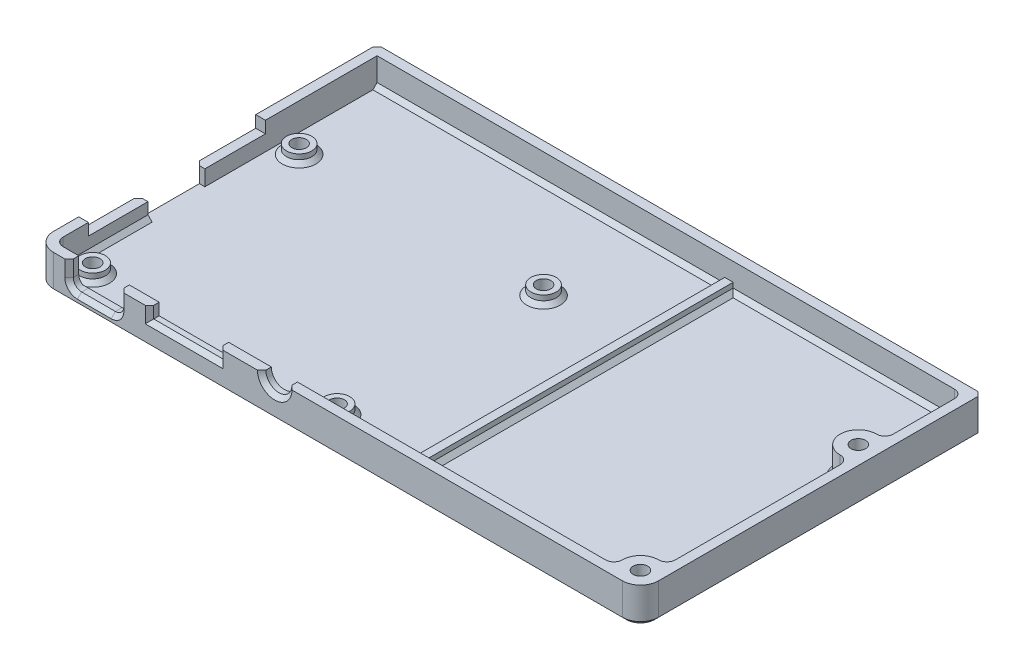
SolidWorks part; units mm, degrees
ref_plane "Front Plane" through (0, 0, 0) normal (0, 0, 1) x (1, 0, 0)
ref_plane "Top Plane" through (0, 0, 0) normal (0, 1, 0) x (1, 0, 0)
ref_plane "Right Plane" through (0, 0, 0) normal (1, 0, 0) x (0, 0, -1)
sketch "Sketch1" plane through (0, 0, 0) normal (0, 1, 0) x (1, 0, 0)
  line L0 (-71.5618, 12.356) -> (65.4382, 12.356) construction
  line L1 (-71.5618, 49.606) -> (65.4382, 49.606)
  line L2 (-71.5618, 49.606) -> (-71.5618, -24.894)
  line L3 (-71.5618, -24.894) -> (65.4382, -24.894)
  line L4 (65.4382, 49.606) -> (65.4382, -24.894)
  line L5 (-60.6618, -24.894) -> (-60.6618, -31.6828) construction
  line L6 (-68.0618, 27.606) -> (-10.0618, 27.606)
  line L7 (-68.0618, 27.606) -> (-68.0618, -21.394)
  line L8 (-68.0618, -21.394) -> (-10.0618, -21.394)
  line L9 (-10.0618, 27.606) -> (-10.0618, -21.394)
  line L10 (-39.5618, -24.894) -> (-39.5618, -31.6828) construction
  line L11 (-18.0618, -24.894) -> (-18.0618, -31.6828) construction
  line L12 (-65.4118, -26.5648) -> (-55.9118, -26.5648) construction
  line L13 (-48.0618, -26.5648) -> (-31.0618, -26.5648) construction
  line L14 (-22.0618, -26.5648) -> (-14.0618, -26.5648) construction
  line L15 (-72.5618, 9.606) -> (-72.5618, -3.394) construction
  line L16 (-71.5618, 12.356) -> (-72.5618, 12.356) construction
  line L17 (-1.5618, 50.5866) -> (-1.5618, 32.5866)
  line L18 (-71.5618, 50.5866) -> (-6.5618, 50.5866)
  line L19 (-71.5618, 50.5866) -> (-71.5618, 32.5866)
  line L20 (-71.5618, 32.5866) -> (-6.5618, 32.5866)
  line L21 (-6.5618, 50.5866) -> (-6.5618, 32.5866)
  line L22 (-1.5618, 32.5866) -> (63.4382, 32.5866)
  line L23 (-1.5618, 50.5866) -> (63.4382, 50.5866)
  line L24 (63.4382, 50.5866) -> (63.4382, 32.5866)
  dimension "D1" = 137
  dimension "D2" = 74.5
  dimension "D3" = 49
  dimension "D4" = 58
  dimension "D5" = 3.5
  dimension "D6" = 3.5
  dimension "D7" = 10.9
  dimension "D8" = 32
  dimension "D9" = 53.5
  dimension "D10" = 2
  dimension "D11" = 13
  dimension "D12" = 9.5
  dimension "D13" = 17
  dimension "D14" = 8
  dimension "D15" = 65
  dimension "D16" = 18
sketch "Sketch3" plane through (0, 0, 0) normal (0, 1, 0) x (1, 0, 0)
  line L4 (68.7382, 52.906) -> (-74.8618, 52.906)
  line L5 (-74.8618, 52.906) -> (-74.8618, -28.194)
  line L6 (-74.8618, -28.194) -> (68.7382, -28.194)
  line L7 (68.7382, -28.194) -> (68.7382, 52.906)
  line L8 (66.4382, 50.606) -> (-72.5618, 50.606)
  line L9 (66.4382, -25.894) -> (66.4382, 50.606)
  line L10 (-72.5618, -25.894) -> (66.4382, -25.894)
  line L11 (-72.5618, 50.606) -> (-72.5618, -25.894)
  line L12 (66.4382, 50.606) -> (-72.5618, 50.606)
  line L13 (66.4382, -25.894) -> (66.4382, 50.606)
  line L14 (-72.5618, -25.894) -> (66.4382, -25.894)
  line L15 (-72.5618, 50.606) -> (-72.5618, -25.894)
  line L16 (-3.0618, 12.356) -> (-3.0618, 52.906) construction
  line L17 (-71.5618, 12.356) -> (65.4382, 12.356) construction
  line L20 (-74.8618, 12.356) -> (52.7382, 12.356) construction
  line L25 (68.7382, -28.194) -> (68.7382, 52.906) construction
  line L26 (66.4382, -25.894) -> (66.4382, 50.606) construction
  dimension "D1" = 1
  dimension "D2" = 2.3
extrude "Boss-Extrude1" add sketch "Sketch3" along normal blind 8.5
sketch "Sketch5" plane through (0, 0, 0) normal (0, 1, 0) x (1, 0, 0)
  line L1 (-72.5618, 50.606) -> (66.4382, 50.606)
  line L2 (-72.5618, 50.606) -> (-72.5618, -25.894)
  line L3 (-72.5618, -25.894) -> (66.4382, -25.894)
  line L4 (66.4382, 50.606) -> (66.4382, -25.894)
extrude "Boss-Extrude2" add sketch "Sketch5" along normal blind 2
sketch "Sketch6" plane through (0, 2, 0) normal (0, 1, 0) x (1, 0, 0)
  circle A0 centre (-68.0618, 27.606) radius 3
  circle A1 centre (-68.0618, -21.394) radius 3
  circle A2 centre (-10.0618, -21.394) radius 3
  circle A3 centre (-10.0618, 27.606) radius 3
extrude "Boss-Extrude3" add sketch "Sketch6" along normal blind 2.2
sketch "Sketch10" plane through (0, 2, 0) normal (0, 1, 0) x (1, 0, 0)
  line L0 (66.4382, 50.606) -> (-72.5618, 50.606) construction
  line L1 (9.9382, 50.606) -> (11.9382, 50.606)
  line L2 (9.9382, 50.606) -> (9.9382, -25.894)
  line L3 (9.9382, -25.894) -> (11.9382, -25.894)
  line L4 (11.9382, 50.606) -> (11.9382, -25.894)
  line L5 (-72.5618, -25.894) -> (66.4382, -25.894) construction
  line L6 (-10.0618, 27.606) -> (-10.0618, -21.394) construction
  dimension "D1" = 2
  dimension "D2" = 20
extrude "Boss-Extrude4" add sketch "Sketch10" along normal blind 2.2
sketch "Sketch11" plane through (0, 0, 28.194) normal (0, 0, 1) x (1, 0, 0)
  line L0 (-74.8618, 8.5) -> (-74.8618, 0) construction
  line L1 (-66.8618, 8.5) -> (-54.8618, 8.5)
  line L2 (-66.8618, 8.5) -> (-66.8618, 2.7)
  line L3 (-66.8618, 2.7) -> (-54.8618, 2.7)
  line L4 (-54.8618, 8.5) -> (-54.8618, 2.7)
  line L5 (-74.8618, 0) -> (68.7382, 0) construction
  line L6 (-60.8618, 8.5) -> (-60.6618, 0) construction
  line L7 (-65.4118, 0) -> (-55.9118, 0) construction
  line L9 (-47.778, 8.5) -> (-31.278, 8.5)
  line L10 (-47.778, 8.5) -> (-47.778, 5.7)
  line L11 (-47.778, 5.7) -> (-31.278, 5.7)
  line L12 (-31.278, 8.5) -> (-31.278, 5.7)
  line L13 (-68.0618, 0) -> (-10.0618, 0) construction
  line L14 (-39.5618, 0) -> (-39.528, 8.5) construction
  line L15 (-48.0618, 0) -> (-31.0618, 0) construction
  line L16 (-18.0618, 0) -> (-18.0618, 8.5) construction
  line L17 (-22.0618, 0) -> (-14.0618, 0) construction
  line L18 (-74.8618, 8.5) -> (68.7382, 8.5) construction
  circle A0 centre (-18.0618, 8.5) radius 3.1
  dimension "D5" = 6.2
  dimension "D1" = 2.7
  dimension "D2" = 12
  dimension "D3" = 5.7
  dimension "D4" = 16.5
  dimension "D6" = 8
  dimension "D7" = 5.8
  dimension "D8" = 2.8
extrude "Cut-Extrude1" cut sketch "Sketch11" against normal up to next
sketch "Sketch12" plane through (-74.8618, 0, 0) normal (-1, 0, 0) x (0, 0, 1)
  line L0 (-3.106, 0) -> (-3.106, 8.5) construction
  line L1 (-27.606, 0) -> (21.394, 0) construction
  line L2 (-52.906, 8.5) -> (28.194, 8.5) construction
  line L3 (-24.106, 5.7) -> (17.894, 5.7)
  line L4 (-9.7329, 5.7) -> (3.7671, 5.7)
  line L5 (-9.7329, 5.7) -> (-9.7329, 2)
  line L6 (-9.7329, 2) -> (3.7671, 2)
  line L7 (3.7671, 5.7) -> (3.7671, 2)
  line L8 (-24.106, 8.5) -> (17.894, 8.5)
  line L9 (-24.106, 8.5) -> (-24.106, 5.7)
  line L10 (-52.906, 0) -> (28.194, 0) construction
  line L11 (17.894, 8.5) -> (17.894, 5.7)
  line L12 (-9.7329, 3.85) -> (3.7671, 3.85) construction
  point P17 (-3.106, 5.7)
  dimension "D1" = 13.5
  dimension "D2" = 5.7
  dimension "D3" = 3.7
  dimension "D4" = 2
extrude "Cut-Extrude2" cut sketch "Sketch12" against normal up to next contours L9 L3 L11 L8 | L7 L6 L5 L4
fillet "Fillet6" radius 2 1 edges at (66.4382, 5.25, -50.606)
fillet "Fillet8" radius 2 1 edges at (-72.5618, 5.25, 25.894)
chamfer "Chamfer1" distance 1 angle 45 4 edges at (-68.0618, 2, 24.394) (-10.0618, 2, 24.394) (-10.0618, 2, -24.606) (-68.0618, 2, -24.606)
sketch "Sketch24" plane through (0, 2, 0) normal (0, 1, 0) x (1, 0, 0)
  line L2 (68.7382, -28.194) -> (68.7382, 52.906) construction
  circle A0 centre (64.4382, -23.894) radius 4.3
  circle A1 centre (64.4382, 27.806) radius 4.3
  dimension "D1" = 4.3
extrude "Boss-Extrude7" add sketch "Sketch24" along normal up to surface (6.5 mm away) up to face at (0.9486, 8.5, -17.8255)
fillet "Fillet21" radius 2 1 edges at (60.6317, 5.25, 25.894)
fillet "Fillet22" radius 2 3 edges at (66.4382, 5.25, 20.0874) (66.4382, 5.25, -23.9994) (66.4382, 5.25, -31.6126)
fillet "Fillet20" radius 4.3 2 edges at (68.7382, 4.25, 28.194) (-74.8618, 4.25, 28.194)
fillet "Fillet23" radius 2 2 edges at (-66.8618, 2.7, 27.044) (-54.8618, 2.7, 27.044)
chamfer "Chamfer5" distance 1 angle 45 17 edges at (-71.976, 2, 25.3082) (-30.3118, 2, 25.894) (-31.3118, 2, -50.606) (9.9382, 2, -12.356) (11.9382, 2, -12.356) (38.1882, 2, -50.606) (35.0382, 2, 25.894) (61.3977, 2, 20.8534) (66.4382, 2, -41.356) (66.4382, 2, -1.956) (60.1382, 2, -27.806) (59.5524, 2, 25.3082) (65.8524, 2, 19.0082) (65.8524, 2, -22.9202) (-72.5618, 2, 13.8305) (65.8524, 2, -50.0202) (65.8524, 2, -32.6918)
hole_wizard "CSK for #4 Flat Head Socket Cap Screw1" positions "Sketch28" profile "Sketch27" countersink size "#4" standard "ANSI Inch"
sketch "Sketch28" plane through (0, 0, 0) normal (0, -1, 0) x (-1, 0, 0)
  point P0 (68.0618, 27.606)
  point P4 (68.0618, -21.394)
  point P12 (-64.4382, -23.894)
  point P15 (10.0618, -21.394)
  point P19 (10.0618, 27.606)
  point P22 (-64.4382, 27.806)
sketch "Sketch27" plane through (-68.0618, 0, -27.606) normal (1, 0, 0) x (0, 0, -1)
  line L0 (0, 0) -> (0, 15.0378)
  line L1 (0, 15.0378) -> (1.7272, 14)
  line L2 (1.7272, 14) -> (1.7272, 1.6305)
  line L3 (1.7272, 1.6305) -> (3.1446, 0)
  line L5 (3.1446, 0) -> (0, 0)
  line L6 (-1.7272, 1.6305) -> (-3.1446, 0) construction
  line L10 (0, 15.0378) -> (-1.7272, 14) construction
  line L11 (0, -6.35) -> (0, 107.95) construction
  dimension "Hole Dia." = 3.4544
  dimension "Hole Depth" = 14
  dimension "Near C'Sink Dia." = 6.2891
  dimension "Near C'Sink Angle" = 82
  dimension "Drill Angle" = 118
chamfer "Chamfer6" distance 1 angle 45 9 edges at (-18.0618, 5.4, 28.194) (-31.278, 7.1, 28.194) (-39.528, 5.7, 28.194) (-47.778, 7.1, 28.194) (-54.8618, 6.6, 28.194) (-60.8618, 2.7, 28.194) (-66.8618, 6.6, 28.194) (-55.4476, 3.2858, 28.194) (-66.276, 3.2858, 28.194)
chamfer "Chamfer8" distance 1 angle 45 3 edges at (-74.8618, 2, -2.9829)
chamfer "Chamfer9" distance 1 angle 45 2 edges at (68.7382, 4.25, -52.906) (-74.8618, 4.25, -52.906)
chamfer "Chamfer10" distance 1 angle 45 6 edges at (-3.0618, 0, -52.906) (68.7382, 0, -14.006) (67.4788, 0, 26.9346) (-3.0618, 0, 28.194) (-73.6023, 0, 26.9346) (-74.8618, 0, -14.006)
